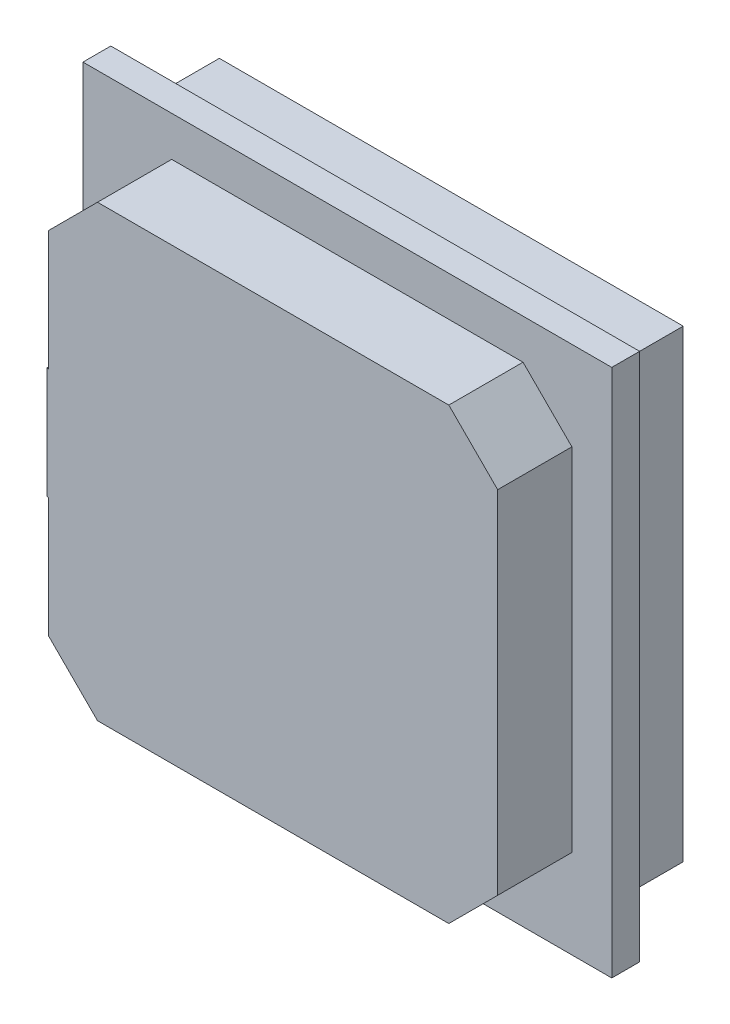
SolidWorks part; units mm, degrees
ref_plane "Alzado" through (0, 0, 0) normal (0, 0, 1) x (1, 0, 0)
ref_plane "Planta" through (0, 0, 0) normal (0, 1, 0) x (1, 0, 0)
ref_plane "Vista lateral" through (0, 0, 0) normal (1, 0, 0) x (0, 0, -1)
sketch "Croquis1" plane through (0, 0, 0) normal (0, 0, 1) x (1, 0, 0)
  line L1 (14.25, -14.25) -> (-14.25, -14.25)
  line L2 (14.25, -14.25) -> (14.25, 14.25)
  line L3 (14.25, 14.25) -> (-14.25, 14.25)
  line L4 (-14.25, -14.25) -> (-14.25, 14.25)
  line L5 (14.25, -14.25) -> (-14.25, 14.25) construction
  line L6 (14.25, 14.25) -> (-14.25, -14.25) construction
  point P0 (0, 0)
  dimension "D1" = 28.5
extrude "Saliente-Extruir1" add sketch "Croquis1" along normal blind 1.5
sketch "Croquis2" plane through (0, 0, 1.5) normal (0, 0, 1) x (1, 0, 0)
  line L0 (-12.1, 9.4668) -> (-9.4668, 12.1)
  line L1 (9.4668, -12.1) -> (-9.4668, -12.1)
  line L2 (12.1, -9.4668) -> (12.1, 9.4668)
  line L3 (9.4668, 12.1) -> (-9.4668, 12.1)
  line L4 (-12.1, -9.4668) -> (-12.1, 9.4668)
  line L5 (12.1, -12.1) -> (-12.1, 12.1) construction
  line L6 (12.1, 12.1) -> (-12.1, -12.1) construction
  line L7 (12.1, -9.4668) -> (9.4668, -12.1)
  line L8 (12.1, -9.4668) -> (12.1, -12.1) construction
  line L9 (-12.1, 9.4668) -> (-12.1, 12.1) construction
  line L10 (-9.4668, -12.1) -> (-12.1, -9.4668)
  line L11 (12.1, 9.4668) -> (9.4668, 12.1)
  line L12 (-12.1, 9.4668) -> (9.4668, -12.1) construction
  line L13 (-12.1, -9.4668) -> (9.4668, 12.1) construction
  line L14 (9.4668, -12.1) -> (12.1, -12.1) construction
  line L15 (-9.4668, -12.1) -> (-12.1, -12.1) construction
  line L16 (-12.1, -12.1) -> (-12.1, -9.4668) construction
  point P0 (0, 0)
  dimension "D1" = 24.2
  dimension "D2" = 30.5
extrude "Saliente-Extruir2" add sketch "Croquis2" along normal blind 4
sketch "Croquis3" plane through (0, 0, 0) normal (0, 0, -1) x (-1, 0, 0)
  line L1 (12.5, -12.5) -> (-12.5, -12.5)
  line L2 (12.5, -12.5) -> (12.5, 12.5)
  line L3 (12.5, 12.5) -> (-12.5, 12.5)
  line L4 (-12.5, -12.5) -> (-12.5, 12.5)
  line L5 (12.5, -12.5) -> (-12.5, 12.5) construction
  line L6 (12.5, 12.5) -> (-12.5, -12.5) construction
  point P0 (0, 0)
  dimension "D1" = 25
extrude "Saliente-Extruir3" add sketch "Croquis3" along normal blind 4.1
sketch "Croquis4" plane through (-12.1, 0, 0) normal (-1, 0, 0) x (0, 0, 1)
  line L0 (1.5, 0) -> (5.5, 0) construction
  line L1 (1.5, 14.25) -> (1.5, -14.25) construction
  line L2 (5.5, 9.4668) -> (5.5, -9.4668) construction
  line L3 (1.5, 9.4668) -> (1.5, -9.4668) construction
  line L4 (5.5, -3) -> (1.5, -3)
  line L5 (5.5, -3) -> (5.5, 3)
  line L6 (5.5, 3) -> (1.5, 3)
  line L7 (1.5, -3) -> (1.5, 3)
  line L8 (5.5, -3) -> (1.5, 3) construction
  line L9 (5.5, 3) -> (1.5, -3) construction
  point P6 (3.5, 0)
  dimension "D1" = 6
extrude "Saliente-Extruir4" add sketch "Croquis4" along normal blind 0.1 contours L6 L7 L4 L5
shell "Vaciado2" thickness 1 removed face at (-12.2, 0, 3.5)
